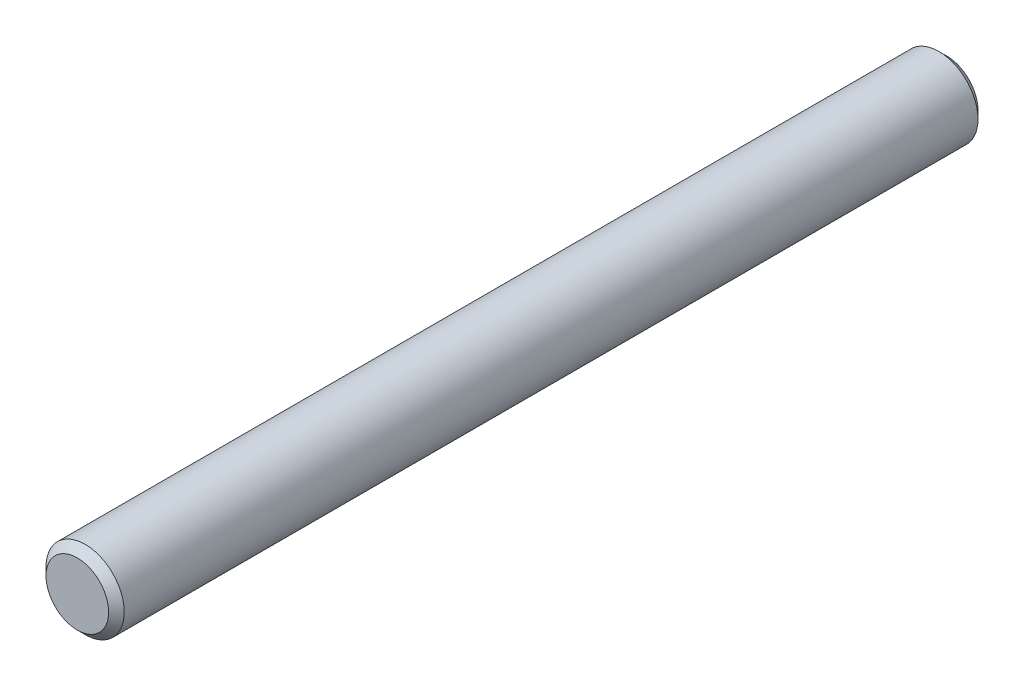
SolidWorks part; units mm, degrees
ref_plane "Front" through (0, 0, 0) normal (0, 0, 1) x (1, 0, 0)
ref_plane "Top" through (0, 0, 0) normal (0, 1, 0) x (1, 0, 0)
ref_plane "Right" through (0, 0, 0) normal (1, 0, 0) x (0, 0, -1)
sketch "Sketch1" plane through (0, 0, 0) normal (0, 0, 1) x (1, 0, 0)
  circle A0 centre (0, 0) radius 4.7625
  dimension "dia" = 9.525
extrude "Extrude1" add sketch "Sketch1" along normal mid plane 105.8
sketch "Sketch2" plane through (0, 0, 0) normal (1, 0, 0) x (0, 0, -1)
  line L0 (-52.9, 4.7625) -> (-47.9, 4.7625) construction
  line L1 (52.9, 4.7625) -> (-52.9, 4.7625) construction
  line L2 (-47.9, 4.7625) -> (-47.9, -4.7625) construction
  line L3 (-52.9, -4.7625) -> (52.9, -4.7625) construction
  point P0 (-52.9, 4.7625)
  point P1 (52.9, 4.7625)
  dimension "D1" = 5
chamfer "Chamfer1" distance 0.9525 angle 45 2 edges at (4.7625, 0, -52.9) (4.7625, 0, 52.9)
equation "\"D1@Chamfer1\" = \"dia@Sketch1\" * .1"
